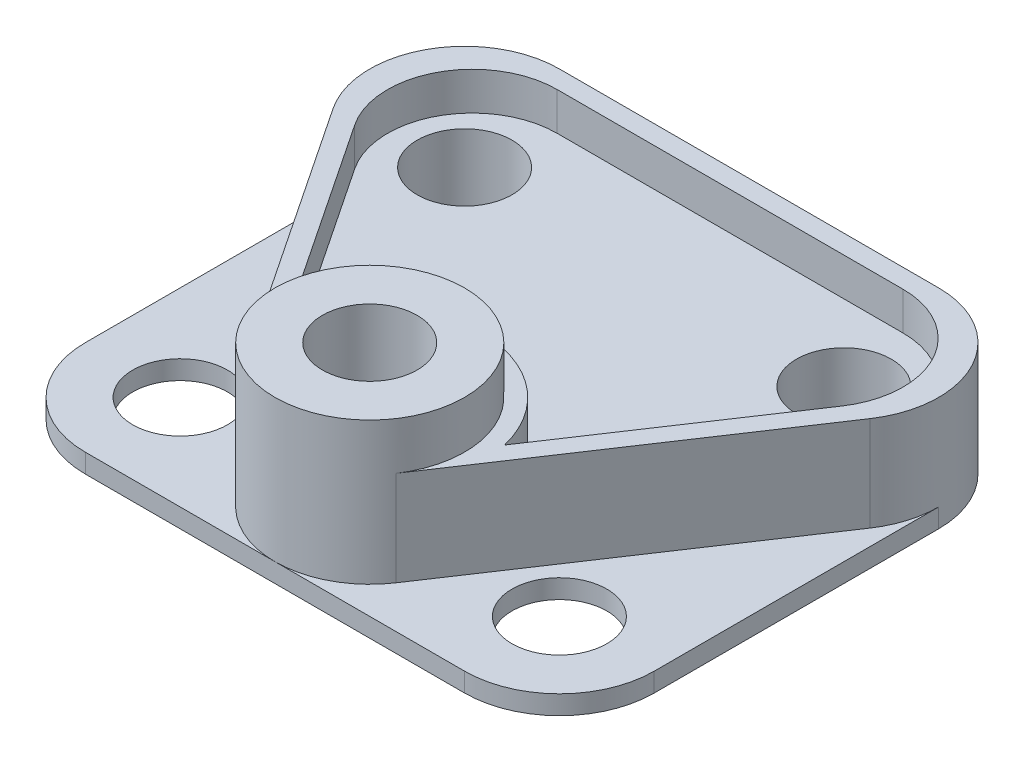
SolidWorks part; units mm, degrees
material "Plain Carbon Steel"
ref_plane "Front Plane" through (0, 0, 0) normal (0, 0, 1) x (1, 0, 0)
ref_plane "Top Plane" through (0, 0, 0) normal (0, 1, 0) x (1, 0, 0)
ref_plane "Right Plane" through (0, 0, 0) normal (1, 0, 0) x (0, 0, -1)
sketch "Sketch1" plane through (0, 0, 0) normal (0, 1, 0) x (1, 0, 0)
  line L1 (12.7, 0) -> (63.5, 0)
  line L2 (0, 12.7) -> (0, 50.8)
  line L3 (12.7, 63.5) -> (63.5, 63.5)
  line L4 (76.2, 12.7) -> (76.2, 50.8)
  arc A0 (0, 50.8) -> (12.7, 63.5) centre (12.7, 50.8) cw
  arc A1 (63.5, 63.5) -> (76.2, 50.8) centre (63.5, 50.8) cw
  arc A2 (63.5, 0) -> (76.2, 12.7) centre (63.5, 12.7) ccw
  arc A3 (12.7, 0) -> (0, 12.7) centre (12.7, 12.7) cw
  circle A4 centre (12.7, 12.7) radius 6.35
  circle A5 centre (63.5, 12.7) radius 6.35
  point P7 (0, 63.5)
  point P12 (76.2, 0)
  point P15 (0, 0)
  dimension "D3" = 12.7
  dimension "D4" = 12.7
  dimension "D1" = 76.2
  dimension "D2" = 63.5
extrude "Boss-Extrude1" add sketch "Sketch1" along normal blind 2.54
sketch "Sketch2" plane through (0, 2.54, 0) normal (0, 1, 0) x (1, 0, 0)
  line L0 (12.7, 0) -> (63.5, 0) construction
  line L1 (38.1, 12.7) -> (12.7, 12.7) construction
  line L2 (38.1, 12.7) -> (63.5, 12.7) construction
  line L3 (12.7, 63.5) -> (63.5, 63.5)
  line L4 (2.133, 43.7553) -> (27.533, 5.6553)
  line L5 (74.067, 43.7553) -> (48.667, 5.6553)
  line L6 (5.4886, 43.3009) -> (23.5531, 16.2041)
  line L7 (52.6469, 16.2041) -> (70.7114, 43.3009)
  line L8 (61.2605, 60.96) -> (14.9395, 60.96)
  line L9 (12.7, 63.5) -> (63.5, 63.5)
  arc A0 (12.7, 63.5) -> (2.133, 43.7553) centre (12.7, 50.8) ccw
  arc A1 (74.067, 43.7553) -> (63.5, 63.5) centre (63.5, 50.8) ccw
  circle A2 centre (38.1, 12.7) radius 12.7
  arc A3 (76.2, 50.8) -> (63.5, 63.5) centre (63.5, 50.8) ccw construction
  arc A4 (14.9395, 60.96) -> (5.4886, 43.3009) centre (14.9395, 49.6015) ccw
  arc A5 (12.7, 63.5) -> (0, 50.8) centre (12.7, 50.8) ccw construction
  arc A6 (52.6469, 16.2041) -> (23.5531, 16.2041) centre (38.1, 12.7) ccw
  arc A7 (61.2605, 60.96) -> (70.7114, 43.3009) centre (61.2605, 49.6015) cw
  circle A8 centre (38.1, 12.7) radius 6.35
  circle A11 centre (12.7, 50.8) radius 6.35
  circle A12 centre (63.5, 50.8) radius 6.35
  arc M16 (12.7, 63.5) -> (0, 50.8) centre (12.7, 50.8) ccw
  arc M22 (76.2, 50.8) -> (63.5, 63.5) centre (63.5, 50.8) ccw
  line M23 (63.5, 63.5) -> (12.7, 63.5)
  dimension "D1" = 2.54
  dimension "D4" = 2.54
  dimension "D2" = 2.54
  dimension "D3" = 2.54
  dimension "D5" = 2.54
extrude "Boss-Extrude2" add sketch "Sketch2" along normal blind 12.7 contours A2 L5 A1 A0 L4 L8 A7 L7 A6 L6 A4 M22 M23 M16 region at (38.1, 2.54, -62.5433)
extrude "Boss-Extrude3" add sketch "Sketch2<3>" along normal blind 19.05 contours A2 A8 region at (34.5238, 2.54, -24.5113)
sketch "Sketch2<3>" plane through (0, 2.54, 0) normal (0, 1, 0) x (1, 0, 0) same geometry as "Sketch2"
extrude "Boss-Extrude4" add sketch "Sketch2<5>" along normal blind 7.62 contours A7 L8 A4 L6 A6 L7 A12 A11 region at (38.1, 2.54, -42.4957)
sketch "Sketch2<5>" plane through (0, 2.54, 0) normal (0, 1, 0) x (1, 0, 0) same geometry as "Sketch2"
sketch "Sketch5" plane through (0, 2.54, 0) normal (0, 1, 0) x (1, 0, 0)
  circle A0 centre (12.7, 50.8) radius 6.35
  circle A1 centre (63.5, 50.8) radius 6.35
  circle A2 centre (38.1, 12.7) radius 6.35
extrude "Cut-Extrude1" cut sketch "Sketch5" against normal blind 7.62
